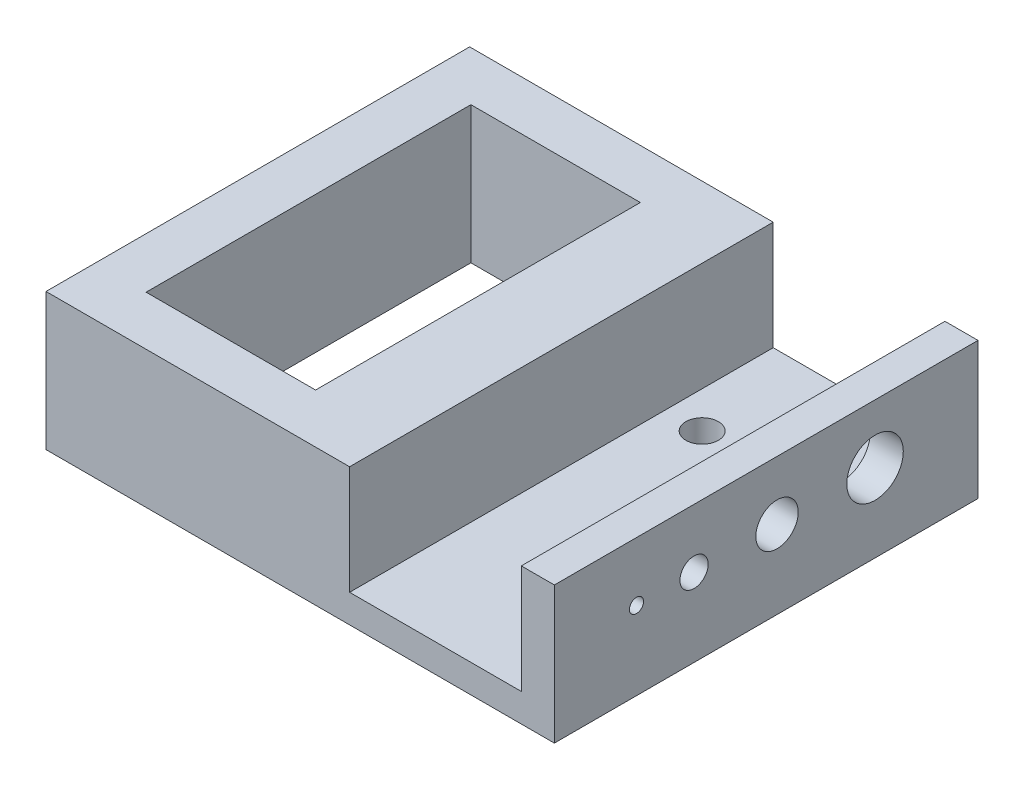
SolidWorks part; units mm, degrees
ref_plane "前视基准面" through (0, 0, 0) normal (0, 0, 1) x (1, 0, 0)
ref_plane "上视基准面" through (0, 0, 0) normal (0, 1, 0) x (1, 0, 0)
ref_plane "右视基准面" through (0, 0, 0) normal (1, 0, 0) x (0, 0, -1)
other "Configuration Table"
sketch "草图1" plane through (0, 0, 0) normal (0, 1, 0) x (1, 0, 0)
  line L0 (-8.4103, 0) -> (-8.4103, 11.5)
  line L1 (-18, 15) -> (18, 15)
  line L2 (-18, 15) -> (-18, -15)
  line L3 (-18, -15) -> (18, -15)
  line L4 (18, 15) -> (18, -15)
  line L5 (-18, 15) -> (18, -15) construction
  line L6 (-18, -15) -> (18, 15) construction
  line L7 (-14.4103, 11.5) -> (-2.4103, 11.5)
  line L8 (-14.4103, 11.5) -> (-14.4103, -11.5)
  line L9 (-14.4103, -11.5) -> (-2.4103, -11.5)
  line L10 (-2.4103, 11.5) -> (-2.4103, -11.5)
  line L11 (-14.4103, 11.5) -> (-2.4103, -11.5) construction
  line L12 (-14.4103, -11.5) -> (-2.4103, 11.5) construction
  line L13 (-8.4103, 11.5) -> (-8.4103, 7.3763)
  line L14 (-8.4103, 7.3763) -> (6.0897, 7.3763)
  circle A0 centre (6.0897, 7.3763) radius 2.55
  point P0 (0, 0)
  point P6 (-8.4103, 0)
  dimension "D1" = 36
  dimension "D2" = 30
  dimension "D3" = 12
  dimension "D4" = 23
  dimension "D5" = 14.5
extrude "凸台-拉伸1" add sketch "草图1" along normal blind 10 contours L4 L1 L2 L3 A0 L10 L9 L8 L7 | A0 region at (6.0897, 0, -9.8542) region at (2.8036, 0, 0.1923)
extrude "凸台-拉伸2" add sketch "草图1<4>" against normal blind 6 contours A0 region at (6.0897, 0, -9.8542)
sketch "草图1<4>" plane through (0, 0, 0) normal (0, 1, 0) x (1, 0, 0) same geometry as "草图1"
sketch "草图2" plane through (0, 10, 0) normal (0, 1, 0) x (1, 0, 0)
  line L1 (3.499, 18.0101) -> (15.6598, 18.0101)
  line L2 (3.499, 18.0101) -> (3.499, -16.6755)
  line L3 (3.499, -16.6755) -> (15.6598, -16.6755)
  line L4 (15.6598, 18.0101) -> (15.6598, -16.6755)
  point P4 (3.499, 18.0101)
extrude "切除-拉伸1" cut sketch "草图2" against normal blind 8
sketch "草图3" plane through (18, 0, 0) normal (1, 0, 0) x (0, 0, -1)
  circle A0 centre (-9.1842, 5.5349) radius 0.5
  circle A1 centre (-5.1072, 5.5349) radius 1
  circle A2 centre (0.7699, 5.5349) radius 1.5
  circle A3 centre (7.7095, 5.5349) radius 2
extrude "切除-拉伸2" cut sketch "草图3" against normal blind 8
sketch "草图4" plane through (0, -6, 0) normal (0, -1, 0) x (1, 0, 0)
  circle A0 centre (5.7954, -7.1285) radius 4.418
extrude "切除-拉伸3" cut sketch "草图4" against normal blind 0.1
sketch "草图5" plane through (0, -5.9, 0) normal (0, -1, 0) x (1, 0, 0)
  circle A0 centre (5.7673, -7.2969) radius 5.0532
extrude "切除-拉伸4" cut sketch "草图5" against normal blind 1.4
sketch "草图6" plane through (0, -4.5, 0) normal (0, -1, 0) x (1, 0, 0)
  circle A0 centre (6.0897, -7.3763) radius 1
extrude "切除-拉伸6" cut sketch "草图6" against normal blind 10
sketch "草图11" plane through (0, -4.5, 0) normal (0, -1, 0) x (1, 0, 0)
  circle A0 centre (6.0897, -7.3763) radius 1
  circle A1 centre (6.0897, -7.3763) radius 2.55
extrude "凸台-拉伸3" add sketch "草图11" along normal blind 5
sketch "草图12" plane through (0, -9.5, 0) normal (0, -1, 0) x (1, 0, 0)
  circle A0 centre (6.0897, -7.3763) radius 2.1
extrude "切除-拉伸7" cut sketch "草图12" against normal blind 9.5 flip side to cut
sketch "草图13" plane through (0, -9.5, 0) normal (0, -1, 0) x (1, 0, 0)
  circle A0 centre (6.0897, -7.3763) radius 1.15
extrude "切除-拉伸8" cut sketch "草图13" against normal blind 13.5
sketch "草图14" plane through (0, 10, 0) normal (0, 1, 0) x (1, 0, 0)
  line L1 (-78.4573, 58.3597) -> (24.2213, 58.3597)
  line L2 (-78.4573, 58.3597) -> (-78.4573, -21.9206)
  line L3 (-78.4573, -21.9206) -> (24.2213, -21.9206)
  line L4 (24.2213, 58.3597) -> (24.2213, -21.9206)
  line L5 (-78.4573, 58.3597) -> (24.2213, -21.9206) construction
  line L6 (-78.4573, -21.9206) -> (24.2213, 58.3597) construction
  point P0 (-27.118, 18.2196)
extrude "切除-拉伸9" cut sketch "草图14" against normal blind 0.3
